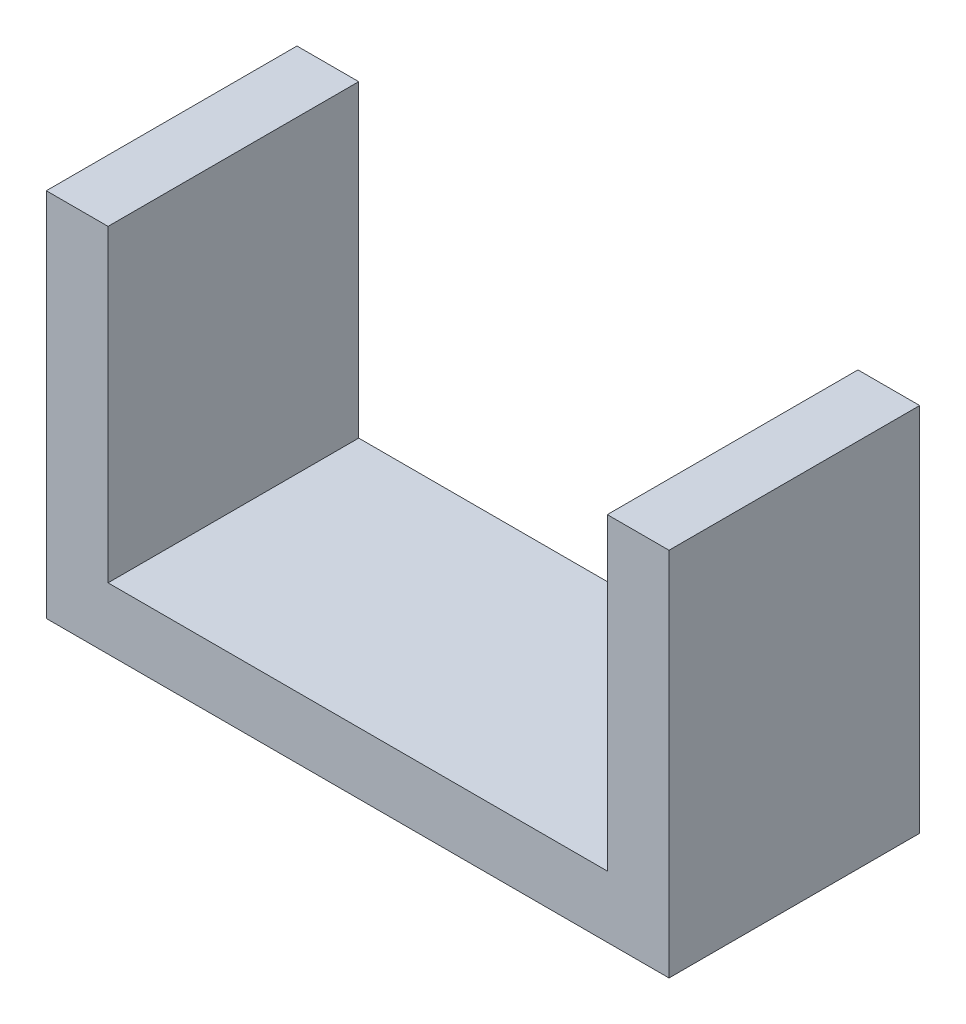
SolidWorks part; units mm, degrees
ref_plane "Front Plane" through (0, 0, 0) normal (0, 0, 1) x (1, 0, 0)
ref_plane "Top Plane" through (0, 0, 0) normal (0, 1, 0) x (1, 0, 0)
ref_plane "Right Plane" through (0, 0, 0) normal (1, 0, 0) x (0, 0, -1)
sketch "Sketch1" plane through (0, 0, 0) normal (0, 1, 0) x (1, 0, 0)
  line L1 (0, 0) -> (50.43, 0)
  line L2 (0, 0) -> (0, 20.3)
  line L3 (0, 20.3) -> (50.43, 20.3)
  line L4 (50.43, 0) -> (50.43, 20.3)
  dimension "D1" = 50.43
  dimension "D2" = 20.3
extrude "YawMount" add sketch "Sketch1" along normal blind 5
sketch "Sketch2" plane through (0, 5, 0) normal (0, 1, 0) x (1, 0, 0)
  line L0 (0, 0) -> (50.43, 0) construction
  line L1 (0, 20.3) -> (5, 20.3)
  line L2 (0, 20.3) -> (0, 0)
  line L3 (0, 0) -> (5, 0)
  line L4 (5, 20.3) -> (5, 0)
  line L6 (50.43, 20.3) -> (45.43, 20.3)
  line L7 (50.43, 20.3) -> (50.43, 0)
  line L8 (50.43, 0) -> (45.43, 0)
  line L9 (45.43, 20.3) -> (45.43, 0)
  dimension "D2" = 5
extrude "BodyConnectors" add sketch "Sketch2" along normal blind 25
equation "\"srv_w\"= 40.43mm'width of Sain Smart SR319"
equation "\"D1@Sketch1\"=\"srv_w\" + \"mnt_thick\"*2"
equation "\"srv_h\"= 40.61mm'height of Sain Smart SR319"
equation "\"srv_d\"= 20.3mm'depth of Sain Smart SR319"
equation "\"D2@Sketch1\"=\"srv_d\""
equation "\"mnt_thick\"= 5mm'thickness of bracket"
equation "\"D1@YawMount\" = \"mnt_thick\""
equation "\"D2@Sketch2\"=\"mnt_thick\""
equation "\"D1@Sketch2\"=\"mnt_thick\""
